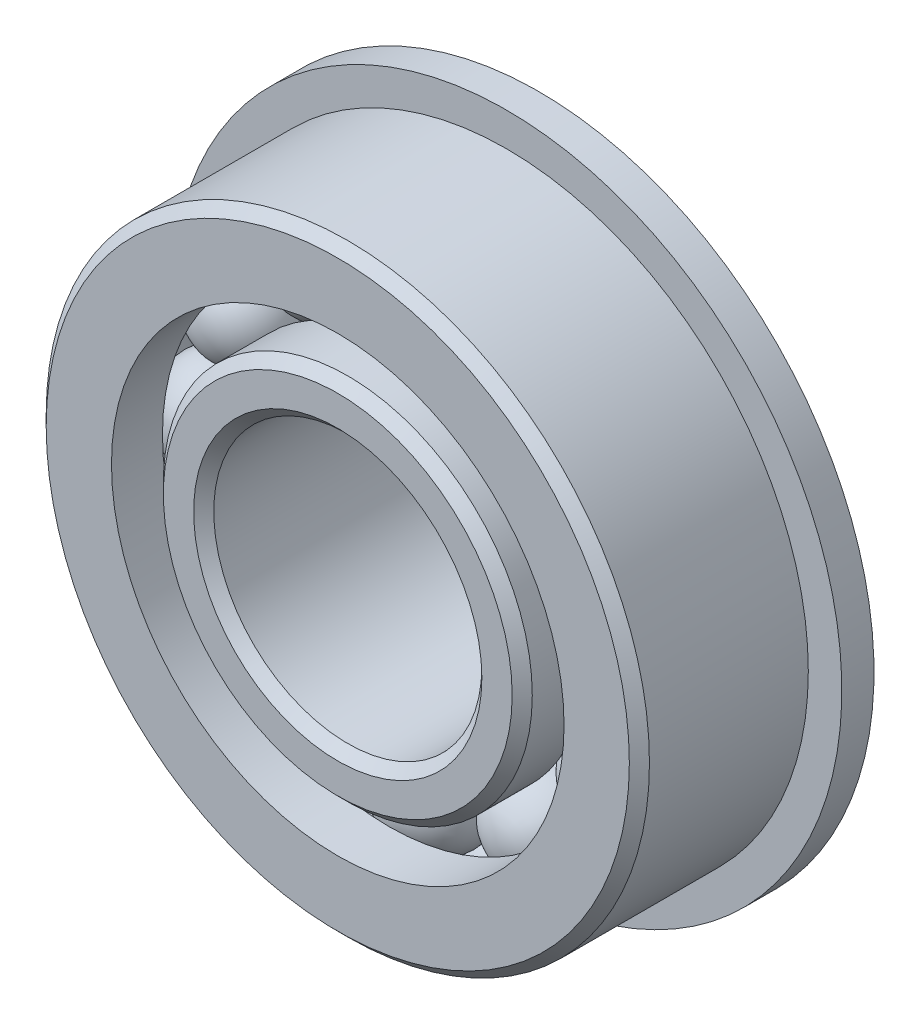
SolidWorks part; units mm, degrees
ref_plane "Front Plane" through (0, 0, 0) normal (0, 0, 1) x (1, 0, 0)
ref_plane "Top Plane" through (0, 0, 0) normal (0, 1, 0) x (1, 0, 0)
ref_plane "Right Plane" through (0, 0, 0) normal (1, 0, 0) x (0, 0, -1)
sketch "Sketch1" plane through (0, 0, 0) normal (1, 0, 0) x (0, 0, -1)
  line L0 (-4.7625, 0) -> (4.7625, 0) construction
  line L1 (0, 14.2875) -> (0, -14.2875) construction
  line L2 (4.2863, 14.2875) -> (-4.2862, 14.2875)
  line L3 (-4.2862, 14.2875) -> (-4.7625, 13.8112)
  line L4 (-4.7625, 13.8112) -> (-4.7625, 10.7188)
  line L5 (-4.7625, 10.7188) -> (-2.3474, 10.7188)
  line L6 (4.7625, 10.7188) -> (2.3474, 10.7188)
  line L7 (4.7625, 13.8113) -> (4.7625, 10.7188)
  line L8 (4.2863, 14.2875) -> (4.7625, 13.8113)
  line L9 (0, 14.2875) -> (0, 10.3187) construction
  line L10 (0, 10.3187) -> (0, 6.35) construction
  line L11 (4.7625, 8.7376) -> (4.7625, -8.7376) construction
  line L12 (-4.7625, 6.35) -> (4.7625, 6.35) construction
  line L13 (0, 7.9375) -> (0, 6.35) construction
  line L14 (0, 12.7) -> (0, 14.2875) construction
  line L15 (4.7625, 8.7376) -> (0, 8.7376) construction
  circle A1 centre (0, 10.3187) radius 2.3813 construction
  arc A2 (-2.3474, 10.7188) -> (2.3474, 10.7188) centre (0, 10.3187) cw
  point P14 (0, 6.35)
  point P22 (0, 7.9375)
  point P23 (0, 12.7)
  dimension "D3" = 4.7625
  dimension "Width" = 9.525
  dimension "OD" = 28.575
  dimension "D1" = 45
  dimension "D2" = 0.4763
  dimension "D4" = 17.4752
  dimension "D5" = 3.9624
  dimension "D6" = 1.9812
revolve "Revolve1" add sketch "Sketch1" angle 360 about L0
sketch "Sketch3" plane through (0, 0, 0) normal (1, 0, 0) x (0, 0, -1)
  line L1 (-4.7625, 13.8112) -> (-4.7625, 10.7188) construction
  line L2 (-4.2862, 14.2875) -> (-4.7625, 13.8112) construction
  line L3 (-4.7625, 9.9187) -> (-4.7625, 6.8262) construction
  line L4 (-4.7625, 6.8262) -> (-4.7625, 8.2614)
  line L5 (-4.7625, 6.8262) -> (-4.2863, 6.35)
  line L6 (-4.2863, 6.35) -> (5.8865, 6.35)
  line L7 (-4.7625, 13.8112) -> (-4.7625, -13.8112) construction
  line L8 (5.8865, 6.35) -> (6.3627, 6.8262)
  line L9 (0, 0) -> (6.3627, 0) construction
  line L13 (4.2863, 14.2875) -> (4.7625, 13.8113) construction
  line L14 (-4.7625, 8.2614) -> (-4.2863, 8.7376)
  line L15 (-4.2863, 8.7376) -> (-1.7805, 8.7376)
  line L16 (1.7805, 8.7376) -> (5.8864, 8.7376)
  line L17 (5.8864, 8.7376) -> (6.3627, 8.2614)
  line L18 (6.3627, 8.2614) -> (6.3627, 6.8262)
  circle A0 centre (0, 10.3187) radius 2.3812 construction
  arc A1 (-1.7805, 8.7376) -> (1.7805, 8.7376) centre (0, 10.3187) ccw
  dimension "D1" = 45
  dimension "Ring Wd" = 11.1252
  dimension "Inner Ring OD" = 17.4752
revolve "Revolve3" add sketch "Sketch3" angle 360 about L0
sketch "Sketch6" plane through (0, 0, 0) normal (1, 0, 0) x (0, 0, -1)
  line L1 (4.7625, 10.7188) -> (3.2385, 10.7188)
  line L2 (4.7625, 10.7188) -> (4.7625, 15.875)
  line L3 (4.7625, 15.875) -> (3.2385, 15.875)
  line L4 (3.2385, 10.7188) -> (3.2385, 15.875)
  line L5 (4.7625, 0) -> (-4.7625, 0) construction
  dimension "Flange OD" = 31.75
  dimension "Flange Thickness" = 1.524
revolve "Revolve6" add sketch "Sketch6" angle 360 about L5
sketch "Sketch4" plane through (0, 0, 0) normal (1, 0, 0) x (0, 0, -1)
  line L0 (-2.3813, 10.3187) -> (2.3813, 10.3187)
  circle A0 centre (0, 10.3187) radius 2.3812 construction
  arc A1 (2.3813, 10.3187) -> (-2.3813, 10.3187) centre (0, 10.3187) ccw
revolve "Revolve4" add sketch "Sketch4" angle 360 about L0
ref_axis "Axis1" through (0, 0, -4.7625) along (0, 0, 1)
pattern_circular "CirPattern1" count 12 every 30 about axis through (0, 0, -4.7625) along (0, 0, 1) of bodies 104
sketch "Sketch5" plane through (0, 0, 0) normal (1, 0, 0) x (0, 0, -1)
  line L0 (-4.7625, 10.7188) -> (-2.3474, 10.7188) construction
  line L1 (-4.5244, 10.7188) -> (-1.7805, 10.7188)
  line L2 (-4.5244, 10.7188) -> (-4.5244, 8.7376)
  line L3 (-4.5244, 8.7376) -> (-1.7805, 8.7376)
  line L4 (-1.7805, 10.7188) -> (-1.7805, 8.7376)
  line L6 (4.7625, 10.7188) -> (2.3474, 10.7188) construction
  line L7 (4.5244, 10.7188) -> (1.7805, 10.7188)
  line L8 (4.5244, 10.7188) -> (4.5244, 8.7376)
  line L9 (4.5244, 8.7376) -> (1.7805, 8.7376)
  line L10 (1.7805, 10.7188) -> (1.7805, 8.7376)
  line L12 (-4.2862, 14.2875) -> (-4.7625, 13.8112) construction
  line L13 (4.7625, 8.7376) -> (0, 8.7376) construction
  line L15 (-4.2863, 8.7376) -> (-1.7805, 8.7376) construction
  line L16 (4.5244, 10.7188) -> (4.5244, 14.0494) construction
  line L17 (4.2863, 14.2875) -> (4.7625, 13.8113) construction
  point P18 (-4.5244, 14.0494)
revolve "Revolve5" [suppressed] add sketch "Sketch5" angle 360 about L0
equation "\"D2@Sketch1\" = \"Width@Sketch1\"*.05"
equation "\"D2@CirPattern1\" = 360/\"Balls@CirPattern1\""
equation "\"D4@Sketch1\"=\"Inner Ring OD@Sketch3\""
equation "\"D3@Sketch1\"=\"Width@Sketch1\"/2."
equation "\"D6@Sketch1\"=\"D5@Sketch1\"/2"
